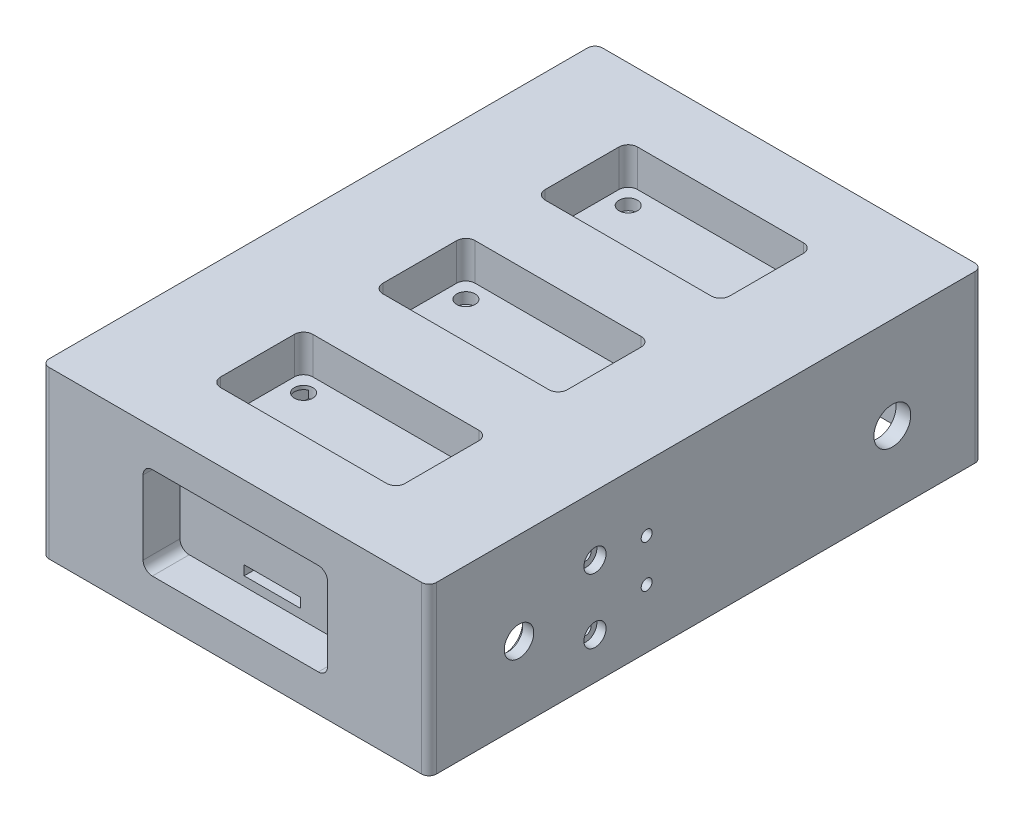
SolidWorks part; units mm, degrees
ref_plane "Спереди" through (0, 0, 0) normal (0, 0, 1) x (1, 0, 0)
ref_plane "Сверху" through (0, 0, 0) normal (0, 1, 0) x (1, 0, 0)
ref_plane "Справа" through (0, 0, 0) normal (1, 0, 0) x (0, 0, -1)
sketch "Эскиз1" plane through (0, 0, 0) normal (0, 1, 0) x (1, 0, 0)
  line L1 (-52.5, -75) -> (52.5, -75)
  line L2 (-52.5, -75) -> (-52.5, 75)
  line L3 (-52.5, 75) -> (52.5, 75)
  line L4 (52.5, -75) -> (52.5, 75)
  line L5 (-52.5, -75) -> (52.5, 75) construction
  line L6 (-52.5, 75) -> (52.5, -75) construction
  point P0 (0, 0)
  dimension "D1" = 105
  dimension "D2" = 150
extrude "Бобышка-Вытянуть1" add sketch "Эскиз1" along normal blind 45
sketch "Эскиз2" plane through (0, 0, 75) normal (0, 0, 1) x (1, 0, 0)
  line L0 (-1050, 22.5) -> (48950, 22.5) construction
  line L1 (-52.5, 45) -> (-52.5, 0) construction
  line L2 (0, -999.2777) -> (0, 49000.7223) construction
  line L4 (-22.5, 10) -> (22.5, 10)
  line L5 (-25, 12.5) -> (-25, 32.5)
  line L6 (-22.5, 35) -> (22.5, 35)
  line L7 (25, 12.5) -> (25, 32.5)
  line L8 (-25, 10) -> (25, 35) construction
  line L9 (-25, 35) -> (25, 10) construction
  arc A0 (-22.5, 35) -> (-25, 32.5) centre (-22.5, 32.5) ccw
  arc A1 (-25, 12.5) -> (-22.5, 10) centre (-22.5, 12.5) ccw
  arc A2 (25, 12.5) -> (22.5, 10) centre (22.5, 12.5) cw
  arc A3 (25, 32.5) -> (22.5, 35) centre (22.5, 32.5) ccw
  point P5 (-52.5, 22.5)
  point P6 (0, 22.5)
  dimension "D3" = 2.5
  dimension "D4" = 2.5
  dimension "D1" = 25
  dimension "D2" = 50
extrude "Вырез-Вытянуть1" cut sketch "Эскиз2" against normal blind 10
sketch "Эскиз4" plane through (0, 45, 0) normal (0, 1, 0) x (1, 0, 0)
  line L0 (0, -1000) -> (0, 49000) construction
  line L1 (-1000, 0) -> (49000, 0) construction
  line L2 (-22.5, 31.5) -> (22.5, 31.5)
  line L3 (-25, 34) -> (-25, 54)
  line L4 (-22.5, 56.5) -> (22.5, 56.5)
  line L5 (-22.5, -12.5) -> (22.5, -12.5)
  line L6 (-25, -10) -> (-25, 10)
  line L7 (-22.5, 12.5) -> (22.5, 12.5)
  line L8 (25, -10) -> (25, 10)
  line L9 (-25, -12.5) -> (25, 12.5) construction
  line L10 (-25, 12.5) -> (25, -12.5) construction
  line L11 (25, 34) -> (25, 54)
  line L12 (-25, 31.5) -> (25, 56.5) construction
  line L13 (-25, 56.5) -> (25, 31.5) construction
  line L14 (-25, -12.5) -> (25, -12.5) [skipped]
  line L15 (-25, -12.5) -> (-25, 12.5) [skipped]
  line L16 (-25, 12.5) -> (25, 12.5) [skipped]
  line L17 (25, -12.5) -> (25, 12.5) [skipped]
  line L18 (-25, -12.5) -> (25, 12.5) construction
  line L19 (-25, 12.5) -> (25, -12.5) construction
  line L20 (-22.5, -56.5) -> (22.5, -56.5)
  line L21 (-25, -54) -> (-25, -34)
  line L22 (-22.5, -31.5) -> (22.5, -31.5)
  line L23 (25, -54) -> (25, -34)
  line L24 (-25, -56.5) -> (25, -31.5) construction
  line L25 (-25, -31.5) -> (25, -56.5) construction
  arc A0 (22.5, -31.5) -> (25, -34) centre (22.5, -34) cw
  arc A1 (25, -54) -> (22.5, -56.5) centre (22.5, -54) cw
  arc A2 (-22.5, -56.5) -> (-25, -54) centre (-22.5, -54) cw
  arc A3 (-25, -34) -> (-22.5, -31.5) centre (-22.5, -34) cw
  arc A4 (-25, 54) -> (-22.5, 56.5) centre (-22.5, 54) cw
  arc A5 (-22.5, 12.5) -> (-25, 10) centre (-22.5, 10) ccw
  arc A6 (25, -10) -> (22.5, -12.5) centre (22.5, -10) cw
  arc A7 (22.5, 56.5) -> (25, 54) centre (22.5, 54) cw
  arc A8 (25, 34) -> (22.5, 31.5) centre (22.5, 34) cw
  arc A9 (-22.5, 31.5) -> (-25, 34) centre (-22.5, 34) cw
  arc A10 (22.5, 12.5) -> (25, 10) centre (22.5, 10) cw
  arc A11 (-22.5, -12.5) -> (-25, -10) centre (-22.5, -10) cw
  point P8 (0, 0)
  point P9 (0, 44)
  point P18 (0, 0)
  point P23 (0, -44)
  dimension "D7" = 2.5
  dimension "D8" = 2.5
  dimension "D1" = 25
  dimension "D2" = 50
  dimension "D5" = 31.5
  dimension "D6" = 31.5
  dimension "D3" = 2
  dimension "D4" = 2
extrude "Вырез-Вытянуть2" cut sketch "Эскиз4" against normal blind 10
mirror "Зеркальное отражение1" about plane through (0, 0, 0) normal (0, 0, 1) of "Вырез-Вытянуть1"
shell "Оболочка1" thickness 4 removed face at (0, 0, 0)
sketch "Эскиз5" plane through (-52.5, 0, 0) normal (-1, 0, 0) x (0, 0, 1)
  line L0 (30, 28.75) -> (30, 11.25) construction
  line L2 (75, 45) -> (75, 0) construction
  line L4 (-75, 0) -> (75, 0) construction
  line L7 (-1075, 20) -> (48925, 20) construction
  line L8 (-75, 45) -> (-75, 0) construction
  circle A3 centre (30, 28.75) radius 1.45
  circle A4 centre (30, 11.25) radius 1.45
  circle A5 centre (50.6, 20) radius 4
  circle A6 centre (-50.6, 20) radius 5
  dimension "D2" = 17.5
  dimension "D3" = 20
  dimension "D6" = 10
  dimension "D1" = 17.5
  dimension "D5" = 2.9
  dimension "D9" = 45
  dimension "D10" = 20.6
  dimension "D11" = 8
  dimension "D4" = 24.4
extrude "Вырез-Вытянуть3" cut sketch "Эскиз5" against normal blind 15
sketch "Эскиз6" plane through (-52.5, 0, 0) normal (-1, 0, 0) x (0, 0, 1)
  circle A2 centre (30, 28.75) radius 3
  circle A3 centre (30, 11.25) radius 3
  dimension "D1" = 6
extrude "Вырез-Вытянуть4" cut sketch "Эскиз6" against normal blind 2.5
sketch "Эскиз10" plane through (0, 31, 0) normal (0, -1, 0) x (-1, 0, 0)
  line L0 (-22.5, -27.5) -> (22.5, -27.5) construction
  line L1 (21, -27.5) -> (26, -27.5)
  line L2 (21, -27.5) -> (21, -64)
  line L3 (21, -64) -> (26, -64)
  line L4 (26, -27.5) -> (26, -64)
  line L5 (21, -27.5) -> (26, -64) construction
  line L6 (21, -64) -> (26, -27.5) construction
  line L7 (29, -34) -> (29, -54) construction
  point P4 (23.5, -45.75)
  dimension "D1" = 36.5
  dimension "D2" = 3
  dimension "D3" = 5
extrude "Вырез-Вытянуть15" cut sketch "Эскиз10" against normal blind 3 and the other way through all
sketch "Эскиз11" plane through (-48.5, 0, 0) normal (1, 0, 0) x (0, 0, -1)
  circle A1 centre (-50.6, 20) radius 5
  dimension "D1" = 10
extrude "Вырез-Вытянуть16" cut sketch "Эскиз11" against normal blind 1
mirror "Зеркальное отражение2" about plane through (0, 0, 0) normal (1, 0, 0) of "Вырез-Вытянуть16", "Вырез-Вытянуть15", "Вырез-Вытянуть4", "Вырез-Вытянуть3"
sketch "Эскиз12" plane through (0, 6, 0) normal (0, -1, 0) x (-1, 0, 0)
  line L0 (-1014.7864, -63) -> (48985.2136, -63) construction
  line L1 (21, -61) -> (-21, -61) construction
  line L2 (0, -1061) -> (0, 48939) construction
  line L3 (-10, -1061) -> (-10, 48939) construction
  line L4 (10, -1061) -> (10, 48939) construction
  circle A0 centre (-10, -63) radius 1.45
  circle A1 centre (10, -63) radius 1.45
  point P7 (0, -61)
  dimension "D4" = 2.9
  dimension "D1" = 2
  dimension "D2" = 20
  dimension "D3" = 10
extrude "Вырез-Вытянуть17" cut sketch "Эскиз12" against normal blind 14
sketch "Эскиз13" plane through (0, 31, 0) normal (0, -1, 0) x (-1, 0, 0)
  line L0 (-1008.6674, -29.5) -> (48991.3326, -29.5) construction
  line L1 (-22.5, -27.5) -> (22.5, -27.5) construction
  line L2 (0, -1027.5) -> (0, 48972.5) construction
  circle A0 centre (-9, -29.5) radius 1.45
  circle A1 centre (9, -29.5) radius 1.45
  point P7 (0, -27.5)
  dimension "D2" = 18
  dimension "D3" = 2.9
  dimension "D1" = 2
  dimension "D4" = 18
extrude "Вырез-Вытянуть18" cut sketch "Эскиз13" against normal blind 10
sketch "Эскиз14" plane through (0, 31, 0) normal (0, -1, 0) x (-1, 0, 0)
  line L0 (20, -957.2029) -> (20, 49042.7971) construction
  line L1 (29, 54) -> (29, 34) construction
  line L2 (-22.5, 60.5) -> (22.5, 60.5) construction
  line L3 (0, -972.5) -> (0, 49027.5) construction
  line L4 (22.5, 27.5) -> (-22.5, 27.5) construction
  line L5 (-20, -957.2029) -> (-20, 49042.7971) construction
  circle A0 centre (20, 47.5) radius 1.45
  circle A1 centre (20, -7.5) radius 1.45
  circle A2 centre (-20, -7.5) radius 1.45
  circle A3 centre (-20, 47.5) radius 1.45
  point P15 (0, 27.5)
  dimension "D1" = 2.9
  dimension "D3" = 9
  dimension "D2" = 55
  dimension "D4" = 13
extrude "Вырез-Вытянуть19" cut sketch "Эскиз14" against normal blind 3
sketch "Эскиз15" plane through (0, 35, 0) normal (0, 1, 0) x (1, 0, 0)
  line L0 (-1010.1672, -54) -> (48989.8328, -54) construction
  line L1 (0, -1031.5) -> (0, 48968.5) construction
  line L2 (-7.6, -55.3) -> (7.6, -55.3)
  line L3 (-7.6, -55.3) -> (-7.6, -52.7)
  line L4 (-7.6, -52.7) -> (7.6, -52.7)
  line L5 (7.6, -55.3) -> (7.6, -52.7)
  line L6 (-7.6, -55.3) -> (7.6, -52.7) construction
  line L7 (-7.6, -52.7) -> (7.6, -55.3) construction
  line L8 (22.5, -31.5) -> (-22.5, -31.5) construction
  line L9 (-22.5, -56.5) -> (22.5, -56.5) construction
  line L10 (-7.6, -10) -> (7.6, -10)
  line L11 (-7.6, -10) -> (-7.6, -7.4)
  line L12 (-7.6, -7.4) -> (7.6, -7.4)
  line L13 (7.6, -10) -> (7.6, -7.4)
  line L14 (-7.6, -10) -> (7.6, -7.4) construction
  line L15 (-7.6, -7.4) -> (7.6, -10) construction
  line L16 (-7.6, 35.3) -> (7.6, 35.3)
  line L17 (-7.6, 35.3) -> (-7.6, 37.9)
  line L18 (-7.6, 37.9) -> (7.6, 37.9)
  line L19 (7.6, 35.3) -> (7.6, 37.9)
  line L20 (-7.6, 35.3) -> (7.6, 37.9) construction
  line L21 (-7.6, 37.9) -> (7.6, 35.3) construction
  line L22 (-22.5, -12.5) -> (22.5, -12.5) construction
  line L23 (22.5, 12.5) -> (-22.5, 12.5) construction
  circle A0 centre (-20, -36.5) radius 2.5
  circle A1 centre (20, -36.5) radius 2.5
  circle A2 centre (-20, 7.5) radius 2.5
  circle A3 centre (20, 7.5) radius 2.5
  circle A4 centre (-20, 51.5) radius 2.5
  circle A5 centre (20, 51.5) radius 2.5
  point P1 (0, -54)
  point P12 (0, -31.5)
  point P16 (0, -8.7)
  point P21 (0, 36.6)
  dimension "D6" = 40
  dimension "D8" = 5
  dimension "D1" = 2.6
  dimension "D2" = 15.2
  dimension "D3" = 2.5
  dimension "D4" = 3
  dimension "D5" = 2.5
  dimension "D7" = 40
  dimension "D9" = 5
  dimension "D10" = 3
  dimension "D11" = 5
extrude "Вырез-Вытянуть20" cut sketch "Эскиз15" against normal blind 3
sketch "Эскиз16" plane through (0, 32, 0) normal (0, 1, 0) x (1, 0, 0)
  line L0 (-7.6, -54) -> (7.6, -54) construction
  line L1 (-7.6, -52.7) -> (-7.6, -55.3) construction
  line L2 (7.6, -55.3) -> (7.6, -52.7) construction
  line L3 (0, -1000) -> (0, 49000) construction
  line L4 (-7, -54.9) -> (7, -54.9)
  line L5 (-7, -54.9) -> (-7, -53.1)
  line L6 (-7, -53.1) -> (7, -53.1)
  line L7 (7, -54.9) -> (7, -53.1)
  line L8 (-7, -54.9) -> (7, -53.1) construction
  line L9 (-7, -53.1) -> (7, -54.9) construction
  line L10 (-7, -9.6) -> (7, -9.6)
  line L11 (-7, -9.6) -> (-7, -7.8)
  line L12 (-7, -7.8) -> (7, -7.8)
  line L13 (7, -9.6) -> (7, -7.8)
  line L14 (-7.6, -8.7) -> (7.6, -8.7) construction
  line L15 (-7, -9.6) -> (7, -7.8) construction
  line L16 (-7, -7.8) -> (7, -9.6) construction
  line L17 (-7, 35.7) -> (7, 35.7)
  line L18 (-7, 35.7) -> (-7, 37.5)
  line L19 (-7, 37.5) -> (7, 37.5)
  line L20 (7, 35.7) -> (7, 37.5)
  line L21 (-7.6, 36.6) -> (7.6, 36.6) construction
  line L22 (-7, 35.7) -> (7, 37.5) construction
  line L23 (-7, 37.5) -> (7, 35.7) construction
  line L24 (-7.6, -7.4) -> (-7.6, -10) construction
  point P6 (0, -54)
  point P17 (0, -8.7)
  point P24 (0, 36.6)
  dimension "D1" = 1.8
  dimension "D2" = 14
  dimension "D3" = 3
extrude "Вырез-Вытянуть21" cut sketch "Эскиз16" against normal blind 3
sketch "Эскиз17" plane through (0, 0, 65) normal (0, 0, 1) x (1, 0, 0)
  line L0 (-7.6, 12.5) -> (7.6, 12.5)
  line L1 (-7.6, 12.5) -> (-7.6, 15.1)
  line L2 (-7.6, 15.1) -> (7.6, 15.1)
  line L3 (7.6, 12.5) -> (7.6, 15.1)
  line L4 (-7.6, 12.5) -> (7.6, 15.1) construction
  line L5 (-7.6, 15.1) -> (7.6, 12.5) construction
  line L8 (-22.5, 10) -> (22.5, 10) construction
  line L9 (0, -965) -> (0, 49035) construction
  line L10 (22.5, 35) -> (-22.5, 35) construction
  circle A0 centre (-20, 30) radius 2.5
  circle A1 centre (20, 30) radius 2.5
  point P0 (0, 13.8)
  point P20 (0, 35)
  dimension "D5" = 5
  dimension "D1" = 2.6
  dimension "D2" = 15.2
  dimension "D3" = 40
  dimension "D4" = 40
  dimension "D6" = 2.5
  dimension "D7" = 5
extrude "Вырез-Вытянуть22" cut sketch "Эскиз17" against normal blind 3
sketch "Эскиз18" plane through (0, 0, 62) normal (0, 0, 1) x (1, 0, 0)
  line L0 (-7.6, 13.8) -> (7.6, 13.8) construction
  line L1 (-7.6, 15.1) -> (-7.6, 12.5) construction
  line L2 (7.6, 12.5) -> (7.6, 15.1) construction
  line L4 (-7, 12.9) -> (7, 12.9)
  line L5 (-7, 12.9) -> (-7, 14.7)
  line L6 (-7, 14.7) -> (7, 14.7)
  line L7 (7, 12.9) -> (7, 14.7)
  line L8 (-7, 12.9) -> (7, 14.7) construction
  line L9 (-7, 14.7) -> (7, 12.9) construction
  point P6 (0, 13.8)
  dimension "D1" = 1.8
  dimension "D2" = 14
extrude "Вырез-Вытянуть23" cut sketch "Эскиз18" against normal blind 3
sketch "Эскиз19" plane through (0, 0, -65) normal (0, 0, -1) x (1, 0, 0)
  line L0 (-7.6, -32.5) -> (7.6, -32.5)
  line L1 (-7.6, -32.5) -> (-7.6, -29.9)
  line L2 (-7.6, -29.9) -> (7.6, -29.9)
  line L3 (7.6, -32.5) -> (7.6, -29.9)
  line L4 (-7.6, -32.5) -> (7.6, -29.9) construction
  line L5 (-7.6, -29.9) -> (7.6, -32.5) construction
  line L6 (0, -1010) -> (0, 48990) construction
  line L7 (-22.5, -10) -> (22.5, -10) construction
  line L10 (22.5, -35) -> (-22.5, -35) construction
  circle A0 centre (-20, -15) radius 2.5
  circle A1 centre (20, -15) radius 2.5
  point P0 (0, -31.2)
  point P14 (0, -10)
  dimension "D5" = 5
  dimension "D7" = 2.5
  dimension "D1" = 2.6
  dimension "D2" = 15.2
  dimension "D3" = 40
  dimension "D4" = 40
  dimension "D6" = 5
extrude "Вырез-Вытянуть24" cut sketch "Эскиз19" against normal blind 3
sketch "Эскиз20" plane through (0, 0, -62) normal (0, 0, -1) x (1, 0, 0)
  line L0 (-1007.6, -31.2) -> (48992.4, -31.2) construction
  line L1 (-7.6, -29.9) -> (-7.6, -32.5) construction
  line L3 (-7, -32.1) -> (7, -32.1)
  line L4 (-7, -32.1) -> (-7, -30.3)
  line L5 (-7, -30.3) -> (7, -30.3)
  line L6 (7, -32.1) -> (7, -30.3)
  line L7 (-7, -32.1) -> (7, -30.3) construction
  line L8 (-7, -30.3) -> (7, -32.1) construction
  line L10 (0, -1029.9) -> (0, 48970.1) construction
  line L11 (7.6, -29.9) -> (-7.6, -29.9) construction
  point P1 (0, -31.2)
  point P5 (-7.6, -31.2)
  point P18 (0, -29.9)
  dimension "D1" = 1.8
  dimension "D2" = 14
extrude "Вырез-Вытянуть25" cut sketch "Эскиз20" against normal blind 8
sketch "Эскиз21" plane through (0, 0, -75) normal (0, 0, -1) x (1, 0, 0)
  line L0 (-975, -22.5) -> (49025, -22.5) construction
  line L1 (37.75, -29.75) -> (47.25, -29.75)
  line L2 (37.75, -29.75) -> (37.75, -15.25)
  line L3 (37.75, -15.25) -> (47.25, -15.25)
  line L4 (47.25, -29.75) -> (47.25, -15.25)
  line L5 (37.75, -29.75) -> (47.25, -15.25) construction
  line L6 (37.75, -15.25) -> (47.25, -29.75) construction
  line L7 (25, -12.5) -> (25, -32.5) construction
  line L8 (42.5, -1022.5) -> (42.5, 48977.5) construction
  line L9 (52.5, -45) -> (52.5, 0) construction
  point P0 (42.5, -22.5)
  point P10 (25, -22.5)
  dimension "D1" = 9.5
  dimension "D2" = 14.5
  dimension "D3" = 10
extrude "Вырез-Вытянуть26" cut sketch "Эскиз21" against normal blind 4
sketch "Эскиз22" plane through (0, 0, 0) normal (0, -1, 0) x (-1, 0, 0)
  line L0 (-50.5, -925) -> (-50.5, 49075) construction
  line L2 (-52.5, -75) -> (-52.5, 75) construction
  line L3 (-1046.2998, 73) -> (48953.7002, 73) construction
  line L4 (-52.5, 75) -> (52.5, 75) construction
  line L5 (50.5, -925) -> (50.5, 49075) construction
  line L6 (52.5, 75) -> (52.5, -75) construction
  line L7 (-1052.5, -73) -> (48947.5, -73) construction
  line L8 (52.5, -75) -> (-52.5, -75) construction
  line L9 (0, -925) -> (0, 49075) construction
  line L10 (-1052.5, 0) -> (48947.5, 0) construction
  circle A0 centre (-50.5, -73) radius 1.425
  circle A1 centre (-50.5, 73) radius 1.425
  circle A2 centre (50.5, 73) radius 1.425
  circle A3 centre (50.5, -73) radius 1.425
  circle A4 centre (0, 73) radius 1.425
  circle A5 centre (0, -73) radius 1.425
  circle A6 centre (-50.5, 0) radius 1.425
  circle A7 centre (50.5, 0) radius 1.425
  point P27 (0, 75)
  point P34 (-52.5, 0)
  dimension "D5" = 2.85
  dimension "D1" = 2
  dimension "D2" = 2
  dimension "D3" = 2
  dimension "D4" = 2
extrude "Вырез-Вытянуть27" cut sketch "Эскиз22" against normal blind 9
sketch "Эскиз24" plane through (-52.5, 0, 0) normal (-1, 0, 0) x (0, 0, 1)
  line L0 (0, -1000) -> (0, 49000) construction
  line L1 (16, -988.2808) -> (16, 49011.7192) construction
  line L2 (-75, 0) -> (75, 0) construction
  circle A0 centre (16, 16) radius 1.475
  circle A1 centre (16, 27.5) radius 1.475
  dimension "D4" = 2.95
  dimension "D1" = 11.5
  dimension "D2" = 16
  dimension "D3" = 16
extrude "Вырез-Вытянуть28" cut sketch "Эскиз24" against normal through all
fillet "Скругление1" radius 2 4 edges at (52.5, 22.5, -75) (-52.5, 22.5, -75) (52.5, 22.5, 75) (-52.5, 22.5, 75)
